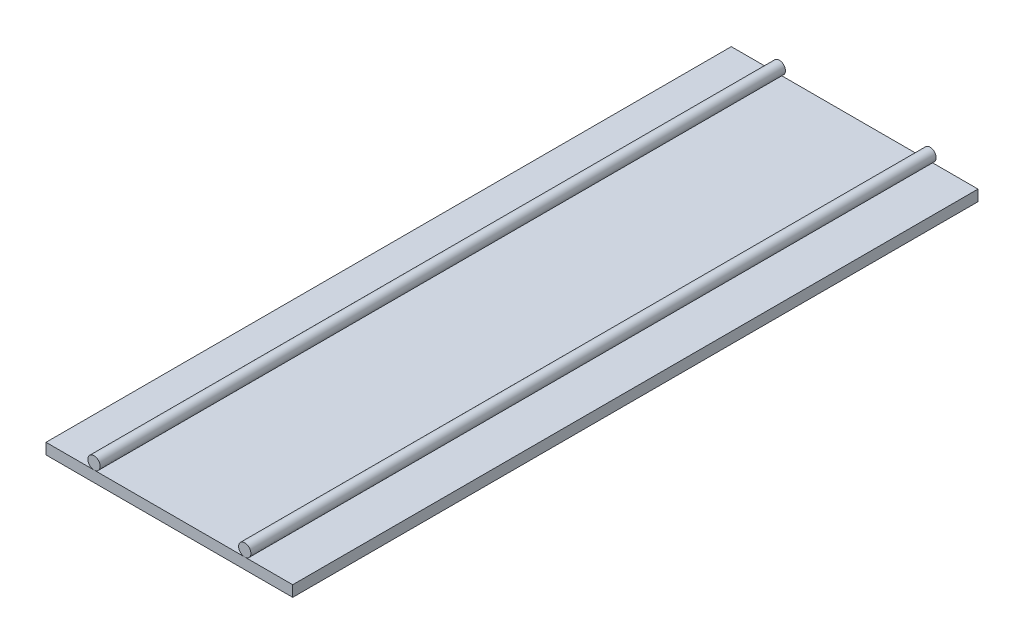
SolidWorks part; units mm, degrees
ref_plane "Płaszczyzna przednia" through (0, 0, 0) normal (0, 0, 1) x (1, 0, 0)
ref_plane "Płaszczyzna górna" through (0, 0, 0) normal (0, 1, 0) x (1, 0, 0)
ref_plane "Płaszczyzna prawa" through (0, 0, 0) normal (1, 0, 0) x (0, 0, -1)
sketch "Szkic1" plane through (0, 0, 0) normal (0, 0, 1) x (1, 0, 0)
  line L0 (-275, 0) -> (275, 0) construction
  circle A0 centre (-275, 0) radius 22.5
  circle A1 centre (275, 0) radius 22.5
  dimension "D1" = 45
  dimension "D2" = 550
extrude "Dodanie-wyciągnięcie1" add sketch "Szkic1" along normal mid plane 2500
sketch "Szkic2" plane through (0, 0, 0) normal (0, 0, 1) x (1, 0, 0)
  line L1 (-450, -22.5) -> (450, -22.5)
  line L2 (-450, -22.5) -> (-450, -62.5)
  line L3 (-450, -62.5) -> (450, -62.5)
  line L4 (450, -22.5) -> (450, -62.5)
  circle A0 centre (-275, 0) radius 22.5 construction
  point P6 (0, -22.5)
  dimension "D1" = 900
  dimension "D2" = 40
extrude "Dodanie-wyciągnięcie2" add sketch "Szkic2" along normal mid plane 2500 separate body
